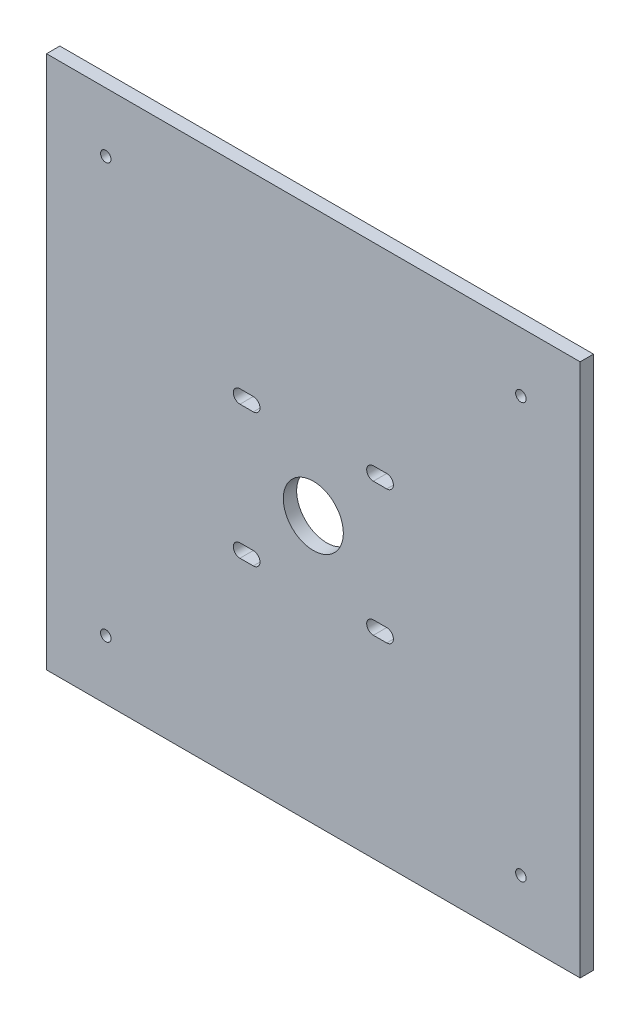
SolidWorks part; units mm, degrees
material "6061-T6 (SS)"
ref_plane "Front Plane" through (0, 0, 0) normal (0, 0, 1) x (1, 0, 0)
ref_plane "Top Plane" through (0, 0, 0) normal (0, 1, 0) x (1, 0, 0)
ref_plane "Right Plane" through (0, 0, 0) normal (1, 0, 0) x (0, 0, -1)
sketch "Sketch1" plane through (0, 0, 0) normal (0, 0, 1) x (1, 0, 0)
  line L0 (0, 49.5808) -> (0, 0) construction
  line L1 (-41.222, 29.6882) -> (0, 49.5808) construction
  line L2 (0, 63.8683) -> (0, 127) construction
  line L3 (-52.2611, 52.5639) -> (-30.1828, 6.8125) construction
  line L4 (-127, -127) -> (127, -127)
  line L5 (-127, -127) -> (-127, 127)
  line L6 (-127, 127) -> (127, 127)
  line L7 (127, -127) -> (127, 127)
  line L8 (-127, -127) -> (127, 127) construction
  line L9 (-127, 127) -> (127, -127) construction
  line L10 (0, -14.2875) -> (0, -127) construction
  line L11 (-41.222, 29.6882) -> (0, 0) construction
  line L13 (-88.9, 17.8308) -> (88.9, 17.8308) construction
  line L14 (-88.9, 17.8308) -> (-88.9, 81.3308) construction
  line L15 (-88.9, 81.3308) -> (88.9, 81.3308) construction
  line L16 (88.9, 17.8308) -> (88.9, 81.3308) construction
  line L17 (-88.9, 17.8308) -> (88.9, 81.3308) construction
  line L18 (-88.9, 81.3308) -> (88.9, 17.8308) construction
  circle A0 centre (0, 0) radius 114.3 construction
  circle A1 centre (0, 0) radius 38.1 construction
  circle A2 centre (0, 49.5808) radius 11.43 construction
  circle A3 centre (0, 49.5808) radius 38.1 construction
  circle A4 centre (-41.222, 29.6882) radius 7.62 construction
  circle A6 centre (-41.222, 29.6882) radius 10.16
  circle A8 centre (-41.222, 29.6882) radius 25.4 construction
  circle A9 centre (-41.222, 29.6882) radius 33.02 construction
  circle A12 centre (-41.222, 29.6882) radius 8.89 construction
  circle A13 centre (0, 0) radius 39.37 construction
  circle A14 centre (0, 49.5808) radius 14.2875
  circle A15 centre (0, 0) radius 127 construction
  circle A16 centre (-98.7828, 98.7828) radius 12.7 construction
  circle A17 centre (-98.7828, 98.7828) radius 6.35 construction
  circle A18 centre (0, 0) radius 14.2875
  circle A19 centre (-98.7828, -98.7828) radius 12.7 construction
  circle A20 centre (-98.7828, -98.7828) radius 6.35 construction
  circle A21 centre (0, 49.5808) radius 39.37 construction
  circle A22 centre (0, 49.5808) radius 12.7 construction
  circle A23 centre (41.222, 29.6882) radius 10.16
  circle A24 centre (-82.55, 74.9808) radius 6.35 construction
  circle A25 centre (82.55, 74.9808) radius 6.35 construction
  circle A26 centre (82.55, 24.1808) radius 6.35 construction
  circle A27 centre (-82.55, 24.1808) radius 6.35 construction
  point P24 (-41.222, 29.6882)
  point P27 (-98.7828, 98.7828)
  point P32 (-98.7828, -98.7828)
  point P33 (-52.2611, 52.5639)
  point P34 (-30.1828, 6.8125)
  point P40 (52.2611, 52.5639)
  point P41 (30.1828, 6.8125)
  point P42 (98.7828, -98.7828)
  point P43 (98.7828, 98.7828)
  point P59 (82.55, 24.1808)
  point P60 (-82.55, 24.1808)
  point P61 (-82.55, 74.9808)
  point P65 (82.55, 74.9808)
  dimension "D1" = 228.6
  dimension "D2" = 76.2
  dimension "D3" = 22.86
  dimension "D5" = 76.2
  dimension "D6" = 15.24
  dimension "D7" = 28.575
  dimension "D8" = 20.32
  dimension "D9" = 25.4
  dimension "D12" = 66.04
  dimension "D13" = 28.575
  dimension "D14" = 50.8
  dimension "D15" = 25.4
  dimension "D18" = 78.74
  dimension "D19" = 17.78
  dimension "D11" = 12.7
  dimension "D20" = 12.7
  dimension "D21" = 78.74
  dimension "D22" = 25.4
  dimension "D26" = 12.7
  dimension "D27" = 12.7
  dimension "D28" = 12.7
  dimension "D29" = 12.7
  dimension "D4" = 49.5808
  dimension "D10" = 45.7708
  dimension "D16" = 254
  dimension "D17" = 254
  dimension "D23" = 50.8
  dimension "D24" = 177.8
  dimension "D25" = 63.5
extrude "Boss-Extrude2" add sketch "Sketch1" along normal blind 6.35 contours L4 L7 L6 L5 A6 A14 A18 A23 | A14 | A23 | A6 region at (-123.4079, 0, 0) region at (-41.222, 29.6882, 0) region at (0, 49.5808, 0) region at (41.222, 29.6882, 0)
hole_wizard "#9 (0.196) Diameter Hole1" positions "Sketch2" profile "Sketch3" hole size "#9" standard "ANSI Inch"
sketch "Sketch2" plane through (0, 0, 0) normal (0, 0, -1) x (-1, 0, 0)
  point P0 (-98.7828, 98.7828)
  point P3 (98.7828, 98.7828)
  point P6 (98.7828, -98.7828)
  point P9 (-98.7828, -98.7828)
sketch "Sketch3" plane through (98.7828, 98.7828, 0) normal (1, 0, 0) x (0, 1, 0)
  line L0 (0, 0) -> (0, 7.8457)
  line L1 (0, 7.8457) -> (2.4892, 6.35)
  line L2 (2.4892, 6.35) -> (2.4892, 0)
  line L5 (2.4892, 0) -> (0, 0)
  line L10 (0, 7.8457) -> (-2.4892, 6.35) construction
  line L11 (0, -6.35) -> (0, 107.95) construction
  dimension "Hole Dia." = 4.9784
  dimension "Hole Depth" = 6.35
  dimension "Drill Angle" = 118
sketch "Sketch4" plane through (0, 0, 6.35) normal (0, 0, 1) x (1, 0, 0)
  line L4 (-34.925, 31.75) -> (-28.575, 31.75) construction
  line L5 (-34.925, 34.925) -> (-28.575, 34.925)
  line L6 (-34.925, 28.575) -> (-28.575, 28.575)
  line L7 (-34.925, -31.75) -> (-28.575, -31.75) construction
  line L8 (-34.925, -28.575) -> (-28.575, -28.575)
  line L9 (-34.925, -34.925) -> (-28.575, -34.925)
  line L10 (28.575, -31.75) -> (34.925, -31.75) construction
  line L11 (28.575, -28.575) -> (34.925, -28.575)
  line L12 (28.575, -34.925) -> (34.925, -34.925)
  line L13 (28.575, 31.75) -> (34.925, 31.75) construction
  line L14 (28.575, 34.925) -> (34.925, 34.925)
  line L15 (28.575, 28.575) -> (34.925, 28.575)
  arc A0 (-34.925, 34.925) -> (-34.925, 28.575) centre (-34.925, 31.75) ccw
  arc A1 (-28.575, 28.575) -> (-28.575, 34.925) centre (-28.575, 31.75) ccw
  arc A2 (-34.925, -28.575) -> (-34.925, -34.925) centre (-34.925, -31.75) ccw
  arc A3 (-28.575, -34.925) -> (-28.575, -28.575) centre (-28.575, -31.75) ccw
  arc A4 (28.575, -28.575) -> (28.575, -34.925) centre (28.575, -31.75) ccw
  arc A5 (34.925, -34.925) -> (34.925, -28.575) centre (34.925, -31.75) ccw
  arc A6 (28.575, 34.925) -> (28.575, 28.575) centre (28.575, 31.75) ccw
  arc A7 (34.925, 28.575) -> (34.925, 34.925) centre (34.925, 31.75) ccw
  point P0 (0, 0)
  point P10 (-31.75, 31.75)
  point P15 (-31.75, -31.75)
  point P22 (31.75, -31.75)
  point P29 (31.75, 31.75)
  dimension "D3" = 3.175
  dimension "D1" = 6.35
  dimension "D2" = 31.75
  dimension "D4" = 63.5
  dimension "D5" = 31.75
  dimension "D6" = 63.5
extrude "Cut-Extrude1" cut sketch "Sketch4" against normal blind 6.35
